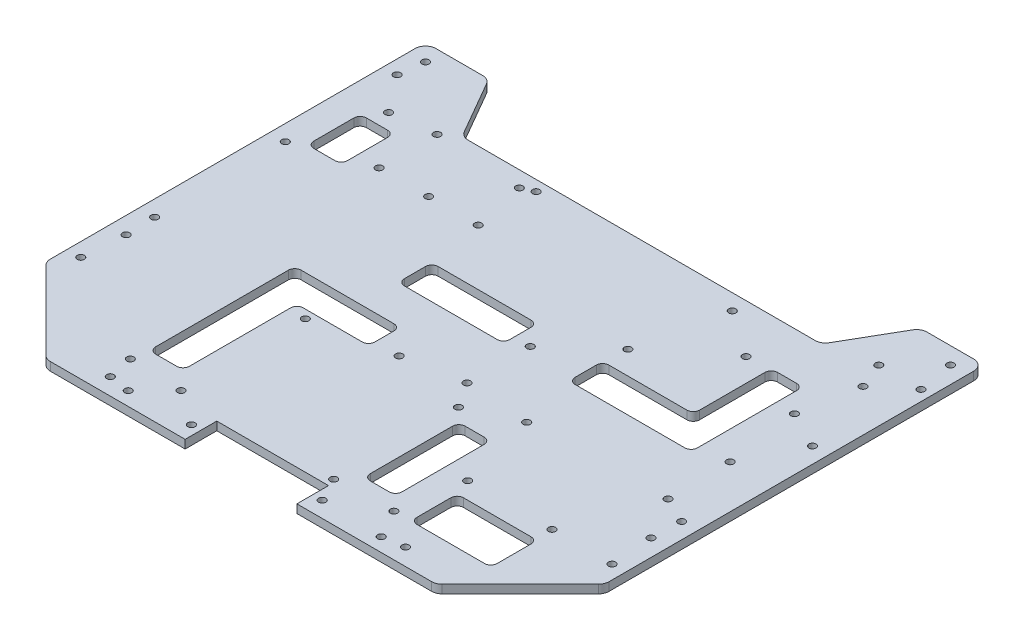
SolidWorks part; units mm, degrees
material "Acier non allié"
ref_plane "Front" through (0, 0, 0) normal (0, 0, 1) x (1, 0, 0)
ref_plane "Top" through (0, 0, 0) normal (0, 1, 0) x (1, 0, 0)
ref_plane "Right" through (0, 0, 0) normal (1, 0, 0) x (0, 0, -1)
sketch "Main scetch" plane through (0, 0, 0) normal (0, 1, 0) x (1, 0, 0)
  line L1 (0, 0) -> (132.5, 0) construction
  line L2 (0, 0) -> (0, 220) construction
  line L3 (0, 220) -> (132.5, 220) construction
  line L4 (132.5, 0) -> (132.5, 220) construction
  line L13 (-92.5, 0) -> (92.5, 0)
  line L14 (92.5, 0) -> (132.5, 40)
  line L15 (132.5, 40) -> (132.5, 220)
  line L16 (132.5, 220) -> (102.5, 220)
  line L17 (102.5, 220) -> (85.1795, 190)
  line L18 (85.1795, 190) -> (-85.1795, 190)
  line L19 (-102.5, 220) -> (-85.1795, 190)
  line L20 (-132.5, 220) -> (-102.5, 220)
  line L21 (-132.5, 40) -> (-132.5, 220)
  line L22 (-92.5, 0) -> (-132.5, 40)
  point P11 (0, 190)
  dimension "132.5" = 132.5
  dimension "D2" = 220
  dimension "D1" = 40
  dimension "D3" = 40
  dimension "D4" = 30
  dimension "D5" = 60
  dimension "D6" = 30
extrude "Main extrusion" add sketch "Main scetch" along normal blind 4
fillet "Congé1" radius 5 10 edges at (-132.5, 2, -40) (-92.5, 2, 0) (92.5, 2, 0) (132.5, 2, -40) (132.5, 2, -220) (102.5, 2, -220) (85.1795, 2, -190) (-85.1795, 2, -190) (-102.5, 2, -220) (-132.5, 2, -220)
sketch "Esquisse1" plane through (0, 4, 0) normal (0, 1, 0) x (1, 0, 0)
  line L0 (0, 0) -> (0, 218.5516) construction
  line L1 (132.5, 42.0711) -> (132.5, 215) construction
  line L2 (127.5, 220) -> (105.3868, 220) construction
  line L3 (-90.4289, 0) -> (90.4289, 0) construction
  circle A0 centre (70, 8) radius 1
  circle A1 centre (124.5, 70) radius 1
  circle A2 centre (124.5, 212) radius 1
  circle A3 centre (-124.5, 212) radius 1
  circle A4 centre (-124.5, 70) radius 1
  circle A5 centre (-70, 8) radius 1
  dimension "D1" = 2
  dimension "D2" = 2
  dimension "D3" = 2
  dimension "D4" = 8
  dimension "D5" = 8
  dimension "D6" = 8
  dimension "D7" = 8
  dimension "D8" = 70
  dimension "D9" = 70
extrude "Enlèv. mat.-Extru.1" cut sketch "Esquisse1" against normal through all
hole_wizard "Dégagement M31" positions "Esquisse2" profile "Esquisse3" hole size "M3" standard "ISO" end condition through all
sketch "Esquisse2" plane through (0, 4, 0) normal (0, 1, 0) x (1, 0, 0)
  point P0 (-124.5, 212)
  point P3 (-124.5, 70)
  point P6 (-70, 8)
  point P9 (70, 8)
  point P12 (124.5, 70)
  point P15 (124.5, 212)
sketch "Esquisse3" plane through (-124.5, 4, -212) normal (1, 0, 0) x (0, 0, 1)
  line L0 (0, 0) -> (0, 4)
  line L1 (0, 4) -> (1.7, 4)
  line L2 (1.7, 4) -> (1.7, 0)
  line L5 (1.7, 0) -> (0, 0)
  line L11 (0, -6.35) -> (0, 107.95) construction
  dimension "Diamètre du perçage jusqu'au prochain" = 3.4
  dimension "Profondeur du perçage jusqu'au prochain" = 4
sketch "Esquisse4" plane through (0, 4, 0) normal (0, 1, 0) x (1, 0, 0)
  line L0 (-132.5, 215) -> (-132.5, 42.0711) construction
  line L1 (-125, 146) -> (-125, 84) construction
  line L2 (82.2927, 190) -> (-82.2927, 190) construction
  line L3 (132.5, 42.0711) -> (132.5, 215) construction
  line L4 (-90.4289, 0) -> (90.4289, 0) construction
  line L5 (127.5, 220) -> (105.3868, 220) construction
  line L8 (-105.3868, 220) -> (-127.5, 220) construction
  line L9 (-31, 7.5) -> (31, 7.5) construction
  line L10 (125, 146) -> (125, 84) construction
  line L11 (-26.5, 0) -> (26.5, 0)
  line L12 (-26.5, 0) -> (-26.5, 15)
  line L13 (-26.5, 15) -> (26.5, 15)
  line L14 (26.5, 0) -> (26.5, 15)
  line L15 (50.5, 182.5) -> (112.5, 182.5) construction
  line L16 (-112.5, 182.5) -> (-50.5, 182.5) construction
  circle A1 centre (-68.5, 185) radius 1 construction
  circle A5 centre (72.5, 167) radius 1
  circle A6 centre (41.5, 142) radius 1
  circle A7 centre (107.5, 155) radius 1
  circle A8 centre (127.5, 195) radius 1
  circle A9 centre (112, 120) radius 1
  circle A10 centre (112.5, 90) radius 1
  circle A11 centre (17.2, 120) radius 1
  circle A12 centre (17.2, 90) radius 1
  circle A13 centre (47.5, 88) radius 1
  circle A14 centre (57.5, 50) radius 1
  circle A15 centre (97.5, 50) radius 1
  circle A16 centre (52.5, 20) radius 1
  circle A17 centre (-10, 85) radius 1
  circle A18 centre (-72.5, 20) radius 1
  circle A19 centre (107.5, 195) radius 1
  circle A23 centre (-47.5, 78) radius 1
  circle A24 centre (25.14, 78) radius 1
  circle A25 centre (-47.5, 19.07) radius 1
  circle A26 centre (25.1096, 18.82) radius 1
  circle A31 centre (-125, 146) radius 1
  circle A32 centre (-125, 84) radius 1
  circle A33 centre (-31, 7.5) radius 1
  circle A34 centre (31, 7.5) radius 1
  circle A35 centre (125, 146) radius 1
  circle A36 centre (125, 84) radius 1
  circle A37 centre (50.5, 182.5) radius 1
  circle A38 centre (112.5, 182.5) radius 1
  circle A39 centre (-112.5, 182.5) radius 1
  circle A40 centre (-50.5, 182.5) radius 1
  circle A41 centre (-45, 185) radius 1
  circle A42 centre (-45, 157.5) radius 1
  circle A43 centre (-68.5, 157.5) radius 1
  circle A44 centre (-92, 157.5) radius 1
  circle A45 centre (-92, 185) radius 1
  circle A46 centre (126, 50) radius 1.5
  circle A47 centre (-60, 6.5) radius 1.5
  circle A48 centre (60, 6.5) radius 1.5
  circle A49 centre (-126, 50) radius 1.5
  circle A50 centre (-126, 200) radius 1.5
  point P63 (-125, 115)
  point P69 (0, 7.5)
  point P74 (0, 15)
  point P79 (125, 115)
  point P104 (-122.3782, 220)
  dimension "D4" = 2
  dimension "D13" = 2
  dimension "D16" = 2
  dimension "D19" = 2
  dimension "D24" = 2
  dimension "D25" = 2
  dimension "D28" = 2
  dimension "D30" = 2
  dimension "D32" = 2
  dimension "D36" = 2
  dimension "D37" = 2
  dimension "D40" = 2
  dimension "D48" = 2
  dimension "D49" = 2
  dimension "D50" = 2
  dimension "D52" = 2
  dimension "D11" = 2
  dimension "D12" = 2
  dimension "D65" = 2
  dimension "D66" = 2
  dimension "D72" = 2
  dimension "D73" = 2
  dimension "D77" = 2
  dimension "D78" = 2
  dimension "D85" = 2
  dimension "D86" = 2
  dimension "D89" = 2
  dimension "D90" = 2
  dimension "D94" = 2
  dimension "D95" = 2
  dimension "D58" = 2
  dimension "D59" = 2
  dimension "D62" = 2
  dimension "D63" = 2
  dimension "D69" = 2
  dimension "D99" = 3
  dimension "D101" = 3
  dimension "D104" = 3
  dimension "D108" = 3
  dimension "D111" = 3
  dimension "D14" = 205
  dimension "D15" = 23
  dimension "D20" = 25
  dimension "D21" = 65
  dimension "D22" = 5
  dimension "D23" = 25
  dimension "D26" = 20.5
  dimension "D27" = 100
  dimension "D29" = 30
  dimension "D31" = 115.3
  dimension "D33" = 115.3
  dimension "D34" = 132
  dimension "D35" = 85
  dimension "D38" = 50
  dimension "D39" = 75
  dimension "D41" = 35
  dimension "D42" = 80
  dimension "D43" = 20
  dimension "D44" = 20
  dimension "D45" = 205
  dimension "D46" = 85
  dimension "D47" = 142.5
  dimension "D51" = 25
  dimension "D53" = 25
  dimension "D54" = 5
  dimension "D55" = 64
  dimension "D7" = 59.18
  dimension "D8" = 72.64
  dimension "D9" = 58.93
  dimension "D10" = 72.61
  dimension "D67" = 85
  dimension "D68" = 78
  dimension "D17" = 25
  dimension "D18" = 31
  dimension "D76" = 62
  dimension "D74" = 7.5
  dimension "D75" = 105
  dimension "D79" = 7.5
  dimension "D80" = 132.5
  dimension "D81" = 62
  dimension "D82" = 15
  dimension "D83" = 53
  dimension "D84" = 62
  dimension "D87" = 7.5
  dimension "D88" = 105
  dimension "D91" = 62
  dimension "D92" = 7.5
  dimension "D96" = 62
  dimension "D97" = 7.5
  dimension "D98" = 20
  dimension "D93" = 20
  dimension "D56" = 87.5
  dimension "D57" = 5
  dimension "D60" = 27.5
  dimension "D61" = 23.5
  dimension "D64" = 23.5
  dimension "D70" = 27.5
  dimension "D71" = 50
  dimension "D100" = 6.5
  dimension "D102" = 6.5
  dimension "D103" = 10
  dimension "D105" = 8
  dimension "D106" = 6.5
  dimension "D107" = 10
  dimension "D109" = 50
  dimension "D110" = 6.5
  dimension "D112" = 6.5
  dimension "D113" = 20
extrude "Enlèv. mat.-Extru.2" cut sketch "Esquisse4" against normal through all
hole_wizard "Dégagement M32" positions "Esquisse5" profile "Esquisse6" hole size "M3" standard "ISO" end condition through all
sketch "Esquisse5" plane through (0, 4, 0) normal (0, 1, 0) x (1, 0, 0)
  point P9 (17.2, 120)
  point P18 (41.5, 142)
  point P21 (72.5, 167)
  point P24 (107.5, 155)
  point P27 (127.5, 195)
  point P30 (112, 120)
  point P33 (112.5, 90)
  point P36 (47.5, 88)
  point P39 (17.2, 90)
  point P42 (57.5, 50)
  point P45 (97.5, 50)
  point P48 (-10, 85)
  point P51 (-72.5, 20)
  point P54 (52.5, 20)
  point P57 (107.5, 195)
  point P86 (-47.5, 78)
  point P89 (25.14, 78)
  point P92 (-47.5, 19.07)
  point P95 (25.1096, 18.82)
  point P114 (-125, 146)
  point P117 (-125, 84)
  point P121 (-31, 7.5)
  point P124 (31, 7.5)
  point P128 (125, 146)
  point P131 (125, 84)
  point P134 (-112.5, 182.5)
  point P137 (-50.5, 182.5)
  point P140 (50.5, 182.5)
  point P143 (112.5, 182.5)
  point P146 (-92, 185)
  point P149 (-92, 157.5)
  point P152 (-68.5, 157.5)
  point P155 (-45, 157.5)
  point P158 (-45, 185)
  point P161 (126, 50)
  point P164 (-60, 6.5)
  point P167 (60, 6.5)
  point P171 (-126, 200)
  point P177 (-126, 50)
sketch "Esquisse6" plane through (17.2, 4, -120) normal (1, 0, 0) x (0, 0, 1)
  line L0 (0, 0) -> (0, 4)
  line L1 (0, 4) -> (1.7, 4)
  line L2 (1.7, 4) -> (1.7, 0)
  line L5 (1.7, 0) -> (0, 0)
  line L11 (0, -6.35) -> (0, 107.95) construction
  dimension "Diamètre du perçage jusqu'au prochain" = 3.4
  dimension "Profondeur du perçage jusqu'au prochain" = 4
sketch "Esquisse7" plane through (0, 4, 0) normal (0, 1, 0) x (1, 0, 0)
  line L0 (-90.4289, 0) -> (-26.5, 0) construction
  line L1 (-40.5, 131) -> (9.5, 131)
  line L2 (-40.5, 131) -> (-40.5, 115)
  line L3 (-40.5, 115) -> (9.5, 115)
  line L4 (9.5, 131) -> (9.5, 115)
  line L5 (-132.5, 215) -> (-132.5, 42.0711) construction
  line L8 (40.5, 115) -> (98.5, 115)
  line L10 (132.5, 42.0711) -> (132.5, 215) construction
  line L11 (40.5, 115) -> (40.5, 131)
  line L12 (83.5, 168) -> (98.5, 168)
  line L13 (83.5, 168) -> (83.5, 131)
  line L15 (98.5, 168) -> (98.5, 115)
  line L16 (40.5, 131) -> (83.5, 131)
  line L17 (-105.3868, 220) -> (-127.5, 220) construction
  line L18 (60.5, 42) -> (98.5, 42)
  line L19 (60.5, 42) -> (60.5, 20)
  line L20 (60.5, 20) -> (98.5, 20)
  line L21 (98.5, 42) -> (98.5, 20)
  line L22 (-118.5, 175) -> (-102.5, 175)
  line L23 (-118.5, 175) -> (-118.5, 150)
  line L24 (-118.5, 150) -> (-102.5, 150)
  line L25 (-102.5, 175) -> (-102.5, 150)
  line L27 (-71.5, 28) -> (-55.5, 28)
  line L28 (-71.5, 28) -> (-71.5, 83)
  line L30 (-55.5, 28) -> (-55.5, 82)
  line L31 (31.5, 71.82) -> (46.5, 71.82)
  line L32 (31.5, 71.82) -> (31.5, 26.82)
  line L33 (31.5, 26.82) -> (46.5, 26.82)
  line L34 (46.5, 71.82) -> (46.5, 26.82)
  line L35 (-71.5, 97) -> (-21.5, 97)
  line L36 (-71.5, 97) -> (-71.5, 83)
  line L37 (-55.5, 82) -> (-21.5, 82)
  line L38 (-21.5, 97) -> (-21.5, 82)
  circle A0 centre (-72.5, 20) radius 1.7 construction
  circle A1 centre (-47.5, 78) radius 1.7 construction
  circle A2 centre (25.1096, 18.82) radius 1.7 construction
  circle A3 centre (52.5, 20) radius 1.7 construction
  dimension "D19" = 8
  dimension "D20" = 8
  dimension "D24" = 15
  dimension "D1" = 50
  dimension "D2" = 16
  dimension "D3" = 131
  dimension "D4" = 92
  dimension "D5" = 16
  dimension "D6" = 53
  dimension "D7" = 43
  dimension "D8" = 115
  dimension "D9" = 72
  dimension "D10" = 38
  dimension "D11" = 34
  dimension "D12" = 15
  dimension "D13" = 22
  dimension "D14" = 20
  dimension "D15" = 30
  dimension "D16" = 70
  dimension "D17" = 16
  dimension "D18" = 25
  dimension "D21" = 16
  dimension "D22" = 55
  dimension "D23" = 8
  dimension "6" = 6
  dimension "D25" = 45
  dimension "D26" = 50
  dimension "D27" = 54
  dimension "D28" = 15
extrude "Enlèv. mat.-Extru.3" cut sketch "Esquisse7" against normal up to surface (4 mm away) up to face at (17.2, 0, -118.3)
fillet "Congé2" radius 3 28 edges at (60.5, 2, -42) (60.5, 2, -20) (98.5, 2, -20) (98.5, 2, -42) (98.5, 2, -168) (98.5, 2, -115) (83.5, 2, -168) (40.5, 2, -131) (83.5, 2, -131) (40.5, 2, -115) (-40.5, 2, -115) (9.5, 2, -115) (9.5, 2, -131) (-40.5, 2, -131) (-118.5, 2, -150) (-102.5, 2, -150) (-102.5, 2, -175) (-118.5, 2, -175) (-55.5, 2, -28) (-71.5, 2, -28) (46.5, 2, -26.82) (31.5, 2, -26.82) (46.5, 2, -71.82) (31.5, 2, -71.82) (-21.5, 2, -82) (-21.5, 2, -97) (-55.5, 2, -82) (-71.5, 2, -97)
equation "\"WIDTH\"= 300mm'Total width of the robot"
equation "\"LENGTH\"= 220mm'Total length of the robot"
equation "\"D2@Main scetch\" = \"LENGTH\""
equation "\"CUT_DEPTH\"= 45mm'Depth of the cut on the edges of the plate"
equation "\"Plate_th\"= 3mm'Thickness of the plate"
equation "\"D1\"= \"Plate_th\""
equation "\"D47@Esquisse4\"=(80+205)/2"
